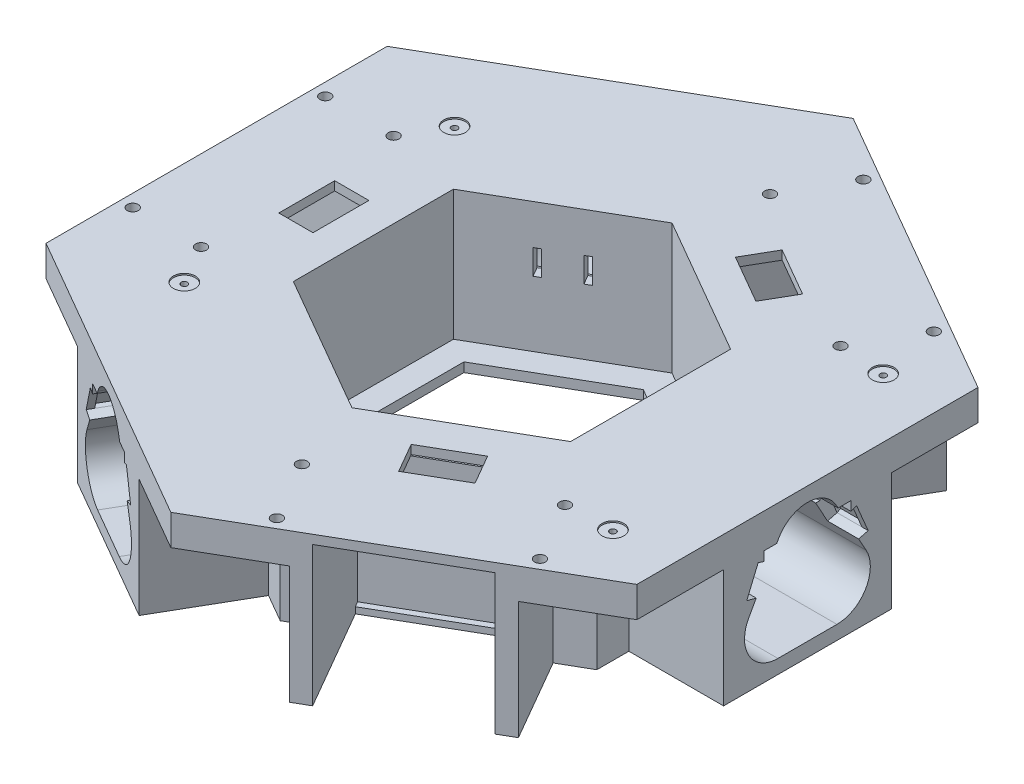
SolidWorks part; units mm, degrees
ref_plane "Plano frontal" through (0, 0, 0) normal (0, 0, 1) x (1, 0, 0)
ref_plane "Plano superior" through (0, 0, 0) normal (0, 1, 0) x (1, 0, 0)
ref_plane "Plano direito" through (0, 0, 0) normal (1, 0, 0) x (0, 0, -1)
sketch "Esboço1" plane through (0, 0, 0) normal (0, 1, 0) x (1, 0, 0)
  line L6 (-95.12, 54.9176) -> (-95.12, -54.9176)
  line L7 (95.12, 54.9176) -> (95.12, -54.9176)
  line L8 (-95.12, 54.9176) -> (0, 109.8351)
  line L9 (0, -109.8351) -> (95.12, -54.9176)
  line L10 (0, -109.8351) -> (-95.12, -54.9176)
  line L11 (95.12, 54.9176) -> (0, 109.8351)
extrude "Ressalto-extrusão1" add sketch "Esboço1" along normal blind 47.85 contours L6 L10 L9 L7 L11 L8
sketch "Esboço2" plane through (0, 47.85, 0) normal (0, 1, 0) x (1, 0, 0)
  line L6 (-36.62, 21.1426) -> (-36.62, -21.1426)
  line L7 (36.62, 21.1426) -> (36.62, -21.1426)
  line L8 (0, -42.2851) -> (36.62, -21.1426)
  line L9 (-36.62, 21.1426) -> (0, 42.2851)
  line L10 (36.62, 21.1426) -> (0, 42.2851)
  line L11 (0, -42.2851) -> (-36.62, -21.1426)
extrude "Corte-extrusão1" cut sketch "Esboço2" against normal through all
sketch "Esboço3" plane through (0, 47.85, 0) normal (0, 1, 0) x (1, 0, 0)
  line L1 (44.62, 25.7614) -> (44.62, -25.7614)
  line L3 (0, -51.5227) -> (-44.62, -25.7614)
  line L5 (44.62, -25.7614) -> (0, -51.5227)
  line L7 (-44.62, -25.7614) -> (-44.62, 25.7614)
  line L9 (-44.62, 25.7614) -> (0, 51.5227)
  line L11 (0, 51.5227) -> (44.62, 25.7614)
extrude "Corte-extrusão2" cut sketch "Esboço3" against normal blind 41.85 contours L11 L1 L5 L3 L7 L9
sketch "Esboço4" plane through (0, 0, 0) normal (0, -1, 0) x (-1, 0, 0)
  line L1 (-44.62, -25.7614) -> (-44.62, 25.7614)
  line L3 (0, 51.5227) -> (44.62, 25.7614)
  line L5 (44.62, 25.7614) -> (44.62, -25.7614)
  line L7 (44.62, -25.7614) -> (0, -51.5227)
  line L9 (-44.62, 25.7614) -> (0, 51.5227)
  line L11 (0, -51.5227) -> (-44.62, -25.7614)
extrude "Corte-extrusão3" cut sketch "Esboço4" against normal blind 3 contours L1 L9 L3 L5 L7 L11
sketch "Esboço5" plane through (-95.12, 0, 0) normal (-1, 0, 0) x (0, 0, 1)
  line L1 (0, 45) -> (-21.5, 45)
  line L2 (0, 45) -> (21.5, 45)
  line L3 (-21.5, 45) -> (-21.5, 0)
  line L4 (-54.9176, 0) -> (54.9176, 0) construction
  line L5 (21.5, 45) -> (21.5, 0)
  line L6 (-21.5, 0) -> (21.5, 0)
extrude "Corte-extrusão4" cut sketch "Esboço5" against normal blind 42.04
sketch "Esboço6" plane through (-53.08, 0, 0) normal (-1, 0, 0) x (0, 0, 1)
  line L0 (0, 0) -> (21.5, 0)
  line L1 (-21.5, 0) -> (21.5, 0) construction
  line L2 (21.5, 0) -> (21.5, 2)
  line L3 (21.5, 0) -> (21.5, 45) construction
  line L4 (0, 0) -> (-21.5, 0)
  line L5 (-21.5, 0) -> (-21.5, 2)
  line L6 (-21.5, 45) -> (-21.5, 0) construction
  line L7 (-21.5, 2) -> (21.5, 2)
extrude "Ressalto-extrusão2" add sketch "Esboço6" along normal blind 2
sketch "Esboço7" plane through (47.56, 0, -82.3763) normal (0.5, 0, -0.866) x (-0.866, 0, -0.5)
  line L1 (0, 45) -> (21.5, 45)
  line L2 (21.5, 45) -> (21.5, 0)
  line L3 (-54.9176, 0) -> (54.9176, 0) construction
  line L4 (0, 45) -> (-21.5, 45)
  line L5 (-21.5, 45) -> (-21.5, 0)
  line L6 (-21.5, 0) -> (21.5, 0)
extrude "Corte-extrusão5" cut sketch "Esboço7" against normal blind 42.04 contours L4 L5 L6 L2 L1
sketch "Esboço8" plane through (47.56, 0, 82.3763) normal (0.5, 0, 0.866) x (0.866, 0, -0.5)
  line L1 (0, 45) -> (21.5, 45)
  line L2 (21.5, 45) -> (21.5, 0)
  line L3 (-54.9176, 0) -> (54.9176, 0) construction
  line L4 (0, 45) -> (-21.5, 45)
  line L5 (-21.5, 45) -> (-21.5, 0)
  line L6 (-21.5, 0) -> (21.5, 0)
extrude "Corte-extrusão6" cut sketch "Esboço8" against normal blind 42.04
sketch "Esboço9" plane through (26.54, 0, 45.9686) normal (0.5, 0, 0.866) x (0.866, 0, -0.5)
  line L0 (0, 0) -> (21.5, 0)
  line L1 (-21.5, 0) -> (21.5, 0) construction
  line L2 (21.5, 0) -> (21.5, 2)
  line L3 (21.5, 0) -> (21.5, 45) construction
  line L4 (0, 0) -> (-21.5, 0)
  line L5 (-21.5, 0) -> (-21.5, 2)
  line L6 (-21.5, 45) -> (-21.5, 0) construction
  line L7 (-21.5, 2) -> (21.5, 2)
extrude "Ressalto-extrusão3" add sketch "Esboço9" along normal blind 2
sketch "Esboço10" plane through (26.54, 0, -45.9686) normal (0.5, 0, -0.866) x (-0.866, 0, -0.5)
  line L0 (0, 0) -> (21.5, 0)
  line L1 (-21.5, 0) -> (21.5, 0) construction
  line L2 (21.5, 0) -> (21.5, 2)
  line L3 (21.5, 45) -> (21.5, 0) construction
  line L4 (0, 0) -> (-21.5, 0)
  line L5 (-21.5, 0) -> (-21.5, 2)
  line L6 (-21.5, 45) -> (-21.5, 0) construction
  line L7 (-21.5, 2) -> (21.5, 2)
extrude "Ressalto-extrusão4" add sketch "Esboço10" along normal blind 2
sketch "Esboço11" plane through (0, 47.85, 0) normal (0, 1, 0) x (1, 0, 0)
  line L1 (-52.58, 0) -> (-52.58, 9)
  line L2 (-52.58, 9) -> (-63.58, 9)
  line L3 (-63.58, 9) -> (-63.58, -9)
  line L4 (-63.58, -9) -> (-52.58, -9)
  line L5 (-52.58, -9) -> (-52.58, 0)
  line L7 (26.29, 45.5356) -> (34.0842, 41.0356)
  line L8 (34.0842, 41.0356) -> (39.5842, 50.5619)
  line L9 (39.5842, 50.5619) -> (23.9958, 59.5619)
  line L10 (23.9958, 59.5619) -> (18.4958, 50.0356)
  line L11 (18.4958, 50.0356) -> (26.29, 45.5356)
  line L13 (26.29, -45.5356) -> (18.4958, -50.0356)
  line L14 (18.4958, -50.0356) -> (23.9958, -59.5619)
  line L15 (23.9958, -59.5619) -> (39.5842, -50.5619)
  line L16 (39.5842, -50.5619) -> (34.0842, -41.0356)
  line L17 (34.0842, -41.0356) -> (26.29, -45.5356)
extrude "Corte-extrusão7" cut sketch "Esboço11" against normal blind 2.85
sketch "Esboço12" plane through (95.12, 0, 0) normal (1, 0, 0) x (0, 0, -1)
  line L10 (-9.3154, 37.762) -> (-18.9028, 20.4605)
  line L11 (9.3154, 37.762) -> (18.9028, 20.4605)
  line L12 (-9.5, 4.5) -> (9.5, 4.5)
  arc A1 (-18.9028, 20.4605) -> (-9.5, 4.5) centre (-9.5, 15.25) ccw
  arc A3 (9.3154, 37.762) -> (-9.3154, 37.762) centre (0, 32.6) ccw
  arc A4 (9.5, 4.5) -> (18.9028, 20.4605) centre (9.5, 15.25) ccw
extrude "Corte-extrusão8" cut sketch "Esboço12" against normal blind 37.5 contours L10 A1 L12 A4 L11 A3
sketch "Esboço13" plane through (-47.56, 0, 82.3763) normal (-0.5, 0, 0.866) x (0.866, 0, 0.5)
  line L2 (-9.3154, 37.762) -> (-18.9028, 20.4605)
  line L4 (9.5, 4.5) -> (-9.5, 4.5)
  line L6 (9.3154, 37.762) -> (18.9028, 20.4605)
  arc A0 (9.3154, 37.762) -> (-9.3154, 37.762) centre (0, 32.6) ccw
  arc A1 (-18.9028, 20.4605) -> (-9.5, 4.5) centre (-9.5, 15.25) ccw
  arc A2 (9.5, 4.5) -> (18.9028, 20.4605) centre (9.5, 15.25) ccw
extrude "Corte-extrusão9" cut sketch "Esboço13" against normal blind 37.5
sketch "Esboço14" plane through (-47.56, 0, -82.3763) normal (-0.5, 0, -0.866) x (-0.866, 0, 0.5)
  line L0 (-9.3154, 37.762) -> (-18.9028, 20.4605)
  line L2 (9.3154, 37.762) -> (18.9028, 20.4605)
  line L4 (9.5, 4.5) -> (-9.5, 4.5)
  arc A0 (9.3154, 37.762) -> (-9.3154, 37.762) centre (0, 32.6) ccw
  arc A1 (-18.9028, 20.4605) -> (-9.5, 4.5) centre (-9.5, 15.25) ccw
  arc A2 (9.5, 4.5) -> (18.9028, 20.4605) centre (9.5, 15.25) ccw
extrude "Corte-extrusão10" cut sketch "Esboço14" against normal blind 37.5
sketch "Esboço15" plane through (95.12, 0, 0) normal (1, 0, 0) x (0, 0, -1)
  line L15 (-9.3154, 37.762) -> (-18.8809, 20.5)
  line L16 (9.3154, 37.762) -> (18.8809, 20.5)
  line L19 (-18.8809, 20.5) -> (18.8809, 20.5)
  arc A0 (9.3154, 37.762) -> (-9.3154, 37.762) centre (0, 32.6) ccw
extrude "Corte-extrusão11" cut sketch "Esboço15" against normal blind 47
sketch "Esboço16" plane through (-47.56, 0, -82.3763) normal (-0.5, 0, -0.866) x (-0.866, 0, 0.5)
  line L2 (9.3154, 37.762) -> (18.9028, 20.4605)
  line L3 (-9.3154, 37.762) -> (-18.9028, 20.4605)
  line L17 (18.8808, 20.5) -> (-18.8808, 20.5)
  arc A1 (-18.8808, 20.5) -> (-18.9028, 20.4605) centre (-9.5, 15.25) ccw
  arc A2 (18.9028, 20.4605) -> (18.8808, 20.5) centre (9.5, 15.25) ccw
  arc A5 (9.3154, 37.762) -> (-9.3154, 37.762) centre (0, 32.6) ccw
extrude "Corte-extrusão12" cut sketch "Esboço16" against normal blind 47 contours L3 A1 L17 A2 L2 A5
sketch "Esboço17" plane through (-47.56, 0, 82.3763) normal (-0.5, 0, 0.866) x (0.866, 0, 0.5)
  line L16 (-9.3154, 37.762) -> (-18.8809, 20.5)
  line L17 (9.3154, 37.762) -> (18.8809, 20.5)
  line L18 (18.8809, 20.5) -> (-18.8809, 20.5)
  arc A2 (9.3154, 37.762) -> (-9.3154, 37.762) centre (0, 32.6) ccw
extrude "Corte-extrusão13" cut sketch "Esboço17" against normal blind 47
sketch "Esboço22" plane through (95.12, 0, 0) normal (1, 0, 0) x (0, 0, -1)
  line L3 (14, 36.75) -> (-14, 36.75)
  line L4 (14, 31.75) -> (-14, 31.75)
  line L8 (14, 36.75) -> (14, 31.75)
  line L10 (-14, 36.75) -> (-14, 31.75)
extrude "Corte-extrusão17" cut sketch "Esboço22" against normal blind 47
sketch "Esboço23" plane through (-47.56, 0, -82.3763) normal (-0.5, 0, -0.866) x (-0.866, 0, 0.5)
  line L3 (14, 36.75) -> (-14, 36.75)
  line L4 (14, 31.75) -> (-14, 31.75)
  line L8 (14, 36.75) -> (14, 31.75)
  line L10 (-14, 36.75) -> (-14, 31.75)
extrude "Corte-extrusão18" cut sketch "Esboço23" against normal blind 47
sketch "Esboço24" plane through (-47.56, 0, 82.3763) normal (-0.5, 0, 0.866) x (0.866, 0, 0.5)
  line L3 (14, 36.75) -> (-14, 36.75)
  line L4 (14, 31.75) -> (-14, 31.75)
  line L8 (14, 36.75) -> (14, 31.75)
  line L10 (-14, 36.75) -> (-14, 31.75)
extrude "Corte-extrusão19" cut sketch "Esboço24" against normal blind 47
sketch "Esboço25" plane through (95.12, 0, 0) normal (1, 0, 0) x (0, 0, -1)
  line L3 (-18.8809, 20.5) -> (18.8809, 20.5) construction
  line L22 (-15.86, 34.37) -> (0, 29.25)
  line L23 (15.86, 34.37) -> (0, 29.25)
  line L24 (-19.55, 25.62) -> (0, 20.5)
  line L25 (0, 20.5) -> (19.55, 25.62)
  line L26 (19.55, 25.62) -> (15.86, 34.37)
  line L27 (-15.86, 34.37) -> (-19.55, 25.62)
extrude "Corte-extrusão20" cut sketch "Esboço25" against normal blind 10
sketch "Esboço26" plane through (-47.56, 0, -82.3763) normal (-0.5, 0, -0.866) x (-0.866, 0, 0.5)
  line L19 (18.8808, 20.5) -> (-18.8808, 20.5) construction
  line L20 (-15.86, 34.37) -> (0, 29.25)
  line L21 (0, 29.25) -> (15.86, 34.37)
  line L22 (-19.55, 25.62) -> (-15.86, 34.37)
  line L23 (-19.55, 25.62) -> (0, 20.5)
  line L24 (0, 20.5) -> (19.55, 25.62)
  line L25 (15.86, 34.37) -> (19.55, 25.62)
extrude "Corte-extrusão21" cut sketch "Esboço26" against normal blind 10 contours L23 L24 L25 L21 L20 L22
sketch "Esboço27" plane through (-47.56, 0, 82.3763) normal (-0.5, 0, 0.866) x (0.866, 0, 0.5)
  line L3 (-15.86, 34.37) -> (0, 29.25)
  line L4 (0, 29.25) -> (15.86, 34.37)
  line L5 (-19.55, 25.62) -> (-15.86, 34.37)
  line L6 (-19.55, 25.62) -> (0, 20.5)
  line L7 (0, 20.5) -> (19.55, 25.62)
  line L8 (15.86, 34.37) -> (19.55, 25.62)
extrude "Corte-extrusão22" cut sketch "Esboço27" against normal blind 10 contours L6 L5 L3 L4 L8 L7
sketch "Esboço28" plane through (22.3184, 10.868, -12.8856) normal (-0.798, -0.3886, 0.4607) x (0.4142, 0.2017, 0.8876)
  line L1 (-79.5509, 34.2548) -> (-89.3084, 36.4438) construction
  line L2 (-87.3569, 36.006) -> (-85.2781, 45.2719)
  line L3 (-77.4722, 43.5207) -> (-87.2296, 45.7097) construction
  line L4 (-85.2781, 45.2719) -> (-77.4722, 43.5207)
  line L5 (-77.4722, 43.5207) -> (-79.5509, 34.2548)
  line L7 (-87.3569, 36.006) -> (-79.5509, 34.2548)
extrude "Corte-extrusão23" cut sketch "Esboço28" against normal blind 1.5 draft 15 contours L5 L7 L2 L4 draft outward yes
sketch "Esboço29" plane through (-22.3184, 10.868, 12.8856) normal (0.798, -0.3886, -0.4607) x (-0.4142, 0.2017, -0.8876)
  line L1 (86.5602, -3.0112) -> (96.3177, -5.2002) construction
  line L2 (94.3662, -4.7624) -> (86.5602, -3.0112)
  line L3 (86.5602, -3.0112) -> (88.639, 6.2547)
  line L4 (88.639, 6.2547) -> (98.3964, 4.0657) construction
  line L5 (88.639, 6.2547) -> (86.5602, -3.0112) construction
  line L6 (88.639, 6.2547) -> (96.4449, 4.5035)
  line L7 (96.4449, 4.5035) -> (94.3662, -4.7624)
extrude "Corte-extrusão24" cut sketch "Esboço29" against normal blind 1.5 draft 15 contours L2 L3 L6 L7 draft outward yes
sketch "Esboço30" plane through (-22.3184, 10.868, -12.8856) normal (0.798, -0.3886, 0.4607) x (0.4142, -0.2017, -0.8876)
  line L1 (-86.5602, -3.0112) -> (-96.3177, -5.2002) construction
  line L2 (-94.3662, -4.7624) -> (-86.5602, -3.0112)
  line L3 (-86.5602, -3.0112) -> (-88.639, 6.2547)
  line L4 (-88.639, 6.2547) -> (-96.4449, 4.5035)
  line L5 (-88.639, 6.2547) -> (-98.3964, 4.0657) construction
  line L6 (-96.4449, 4.5035) -> (-94.3662, -4.7624)
extrude "Corte-extrusão25" cut sketch "Esboço30" against normal blind 1.5 draft 15 draft outward yes
sketch "Esboço31" plane through (22.3184, 10.868, 12.8856) normal (-0.798, -0.3886, -0.4607) x (-0.4142, -0.2017, 0.8876)
  line L1 (77.4722, 43.5207) -> (87.2296, 45.7097) construction
  line L2 (85.2781, 45.2719) -> (77.4722, 43.5207)
  line L3 (77.4722, 43.5207) -> (79.5509, 34.2548)
  line L4 (79.5509, 34.2548) -> (87.3569, 36.006)
  line L5 (79.5509, 34.2548) -> (89.3084, 36.4438) construction
  line L6 (87.3569, 36.006) -> (85.2781, 45.2719)
extrude "Corte-extrusão26" cut sketch "Esboço31" against normal blind 1.5 draft 15 draft outward yes
sketch "Esboço32" plane through (0, 10.868, -25.7711) normal (0, -0.3886, 0.9214) x (1, 0, 0)
  line L1 (85.12, 16.0101) -> (95.12, 16.0101) construction
  line L2 (93.12, 16.0101) -> (85.12, 16.0101)
  line L3 (85.12, 16.0101) -> (85.12, 25.5063)
  line L4 (85.12, 25.5063) -> (93.12, 25.5063)
  line L5 (85.12, 25.5063) -> (95.12, 25.5063) construction
  line L6 (93.12, 25.5063) -> (93.12, 16.0101)
extrude "Corte-extrusão27" cut sketch "Esboço32" against normal blind 1.5 draft 15 draft outward yes
sketch "Esboço33" plane through (0, 10.868, 25.7711) normal (0, -0.3886, -0.9214) x (-1, 0, 0)
  line L0 (-85.12, 16.0101) -> (-93.12, 16.0101)
  line L1 (-85.12, 16.0101) -> (-95.12, 16.0101) construction
  line L2 (-93.12, 16.0101) -> (-93.12, 25.5063)
  line L3 (-85.12, 25.5063) -> (-95.12, 25.5063) construction
  line L4 (-93.12, 25.5063) -> (-85.12, 25.5063)
  line L5 (-85.12, 25.5063) -> (-85.12, 16.0101)
extrude "Corte-extrusão28" cut sketch "Esboço33" against normal blind 1.5 draft 15 draft outward yes
sketch "Esboço34" plane through (95.12, 0, 0) normal (1, 0, 0) x (0, 0, -1)
  line L3 (-5, 27) -> (-5, 35)
  line L4 (-5, 35) -> (-7, 35)
  line L5 (-7, 35) -> (-7, 27)
  line L6 (-7, 27) -> (-5, 27)
  line L8 (5, 27) -> (5, 35)
  line L9 (5, 35) -> (7, 35)
  line L10 (7, 35) -> (7, 27)
  line L11 (5, 27) -> (7, 27)
extrude "Corte-extrusão29" cut sketch "Esboço34" against normal blind 78.5
sketch "Esboço35" plane through (-47.56, 0, -82.3763) normal (-0.5, 0, -0.866) x (-0.866, 0, 0.5)
  line L4 (-5, 27) -> (-5, 35)
  line L5 (-5, 35) -> (-7, 35)
  line L6 (-7, 35) -> (-7, 27)
  line L7 (-7, 27) -> (-5, 27)
  line L9 (5, 27) -> (5, 35)
  line L10 (5, 35) -> (7, 35)
  line L11 (7, 35) -> (7, 27)
  line L12 (5, 27) -> (7, 27)
extrude "Corte-extrusão30" cut sketch "Esboço35" against normal blind 78.5
sketch "Esboço36" plane through (-47.56, 0, 82.3763) normal (-0.5, 0, 0.866) x (0.866, 0, 0.5)
  line L4 (-5, 27) -> (-5, 35)
  line L5 (-5, 35) -> (-7, 35)
  line L6 (-7, 35) -> (-7, 27)
  line L7 (-7, 27) -> (-5, 27)
  line L9 (5, 27) -> (5, 35)
  line L10 (5, 35) -> (7, 35)
  line L11 (7, 35) -> (7, 27)
  line L12 (5, 27) -> (7, 27)
extrude "Corte-extrusão31" cut sketch "Esboço36" against normal blind 78.5
sketch "Esboço38" plane through (0, 0, 0) normal (0, -1, 0) x (-1, 0, 0)
  line L30 (-8.9273, 69.4626) -> (0, 74.6167)
  line L32 (8.9273, 69.4626) -> (0, 74.6167)
  line L46 (64.62, 27) -> (64.62, 37.3084)
  line L47 (126.8267, 27) -> (126.8267, -27)
  line L58 (55.6927, 42.4626) -> (64.62, 37.3084)
  line L61 (64.62, -27) -> (64.62, -37.3084)
  line L64 (8.9273, -69.4626) -> (0, -74.6167)
  line L67 (-55.6927, -42.4626) -> (-64.62, -37.3084)
  line L70 (-64.62, 27) -> (-64.62, 37.3084)
  line L72 (55.6927, -42.4626) -> (64.62, -37.3084)
  line L73 (86.796, -96.3351) -> (40.0306, -123.3351)
  line L74 (-8.9273, -69.4626) -> (0, -74.6167)
  line L75 (-40.0306, -123.3351) -> (-86.796, -96.3351)
  line L76 (-64.62, -27) -> (-64.62, -37.3084)
  line L77 (-40.0306, -123.3351) -> (-8.9273, -69.4626)
  line L78 (-86.796, -96.3351) -> (-55.6927, -42.4626)
  line L79 (-40.0306, 123.3351) -> (-86.796, 96.3351)
  line L80 (-55.6927, 42.4626) -> (-64.62, 37.3084)
  line L81 (-126.8267, 27) -> (-126.8267, -27)
  line L82 (86.796, 96.3351) -> (144.1652, 53.1986)
  line L83 (-86.796, 96.3351) -> (-55.6927, 42.4626)
  line L84 (-40.0306, 123.3351) -> (-8.9273, 69.4626)
  line L85 (144.1652, 53.1986) -> (157.5659, 0)
  line L87 (157.5659, 0) -> (144.1652, -63.213)
  line L88 (-126.8267, -27) -> (-64.62, -27)
  line L89 (-126.8267, 27) -> (-64.62, 27)
  line L90 (144.1652, -63.213) -> (119.6711, -105.6381)
  line L91 (119.6711, -105.6381) -> (86.796, -138.7939)
  line L92 (86.796, -138.7939) -> (8.9273, -147.887)
  line L93 (126.8267, 27) -> (64.62, 27)
  line L94 (126.8267, -27) -> (64.62, -27)
  line L95 (8.9273, -147.887) -> (-79.3373, -147.887)
  line L96 (-79.3373, -147.887) -> (-101.3016, -126.1087)
  line L97 (-101.3016, -126.1087) -> (-135.3677, -74.6167)
  line L98 (40.0306, 123.3351) -> (8.9273, 69.4626)
  line L99 (86.796, 96.3351) -> (55.6927, 42.4626)
  line L100 (-135.3677, -74.6167) -> (-152.3432, -27)
  line L101 (-152.3432, -27) -> (-152.3432, 37.3084)
  line L102 (-152.3432, 37.3084) -> (-101.3016, 133.3327)
  line L103 (86.796, -96.3351) -> (55.6927, -42.4626)
  line L104 (40.0306, -123.3351) -> (8.9273, -69.4626)
  line L105 (-101.3016, 133.3327) -> (-48.9949, 151.9802)
  line L106 (-48.9949, 151.9802) -> (18.3094, 159.8396)
  line L107 (18.3094, 159.8396) -> (40.0306, 123.3351)
extrude "Corte-extrusão37" cut sketch "Esboço38" against normal blind 38
sketch "Esboço42" plane through (0, 47.85, 0) normal (0, 1, 0) x (1, 0, 0)
  circle A0 centre (18.7132, 94.4122) radius 1.75
  circle A1 centre (61.4068, -44.3597) radius 1.75
  circle A2 centre (-91.12, 31) radius 1.75
  circle A3 centre (18.7132, -94.4122) radius 1.75
  circle A5 centre (-91.12, -31) radius 1.75
  circle A6 centre (7.7132, -75.3597) radius 1.75
  circle A7 centre (72.4068, -63.4122) radius 1.75
  circle A9 centre (-69.12, 31) radius 1.75
  circle A10 centre (61.4068, 44.3597) radius 1.75
  circle A12 centre (7.7132, 75.3597) radius 1.75
  circle A13 centre (-69.12, -31) radius 1.75
  circle A14 centre (72.4068, 63.4122) radius 1.75
extrude "Corte-extrusão38" cut sketch "Esboço42" against normal through all
sketch "Esboço43" plane through (0, 47.85, 0) normal (0, 1, 0) x (1, 0, 0)
  circle A0 centre (-62, 43.5) radius 3.5
  circle A1 centre (76, 43.5) radius 3.5
  circle A2 centre (-62, -43.5) radius 3.5
  circle A3 centre (76, -43.5) radius 3.5
extrude "Corte-extrusão39" cut sketch "Esboço43" against normal blind 0.5
sketch "Esboço44" plane through (0, 47.85, 0) normal (0, 1, 0) x (1, 0, 0)
  circle A0 centre (-62, 43.5) radius 1
  circle A1 centre (76, 43.5) radius 1
  circle A2 centre (76, -43.5) radius 1
  circle A3 centre (-62, -43.5) radius 1
extrude "Corte-extrusão40" cut sketch "Esboço44" against normal blind 8
sketch "Esboço45" plane through (26.29, 0, 45.5356) normal (0.5, 0, 0.866) x (0.866, 0, -0.5)
  line L1 (9, 47.85) -> (-9, 47.85)
  line L2 (9, 47.85) -> (9, 45)
  line L3 (9, 45) -> (-9, 45)
  line L4 (-9, 47.85) -> (-9, 45)
extrude "Ressalto-extrusão5" add sketch "Esboço45" along normal blind 2.5
sketch "Esboço46" plane through (31.79, 0, 55.0619) normal (-0.5, 0, -0.866) x (-0.866, 0, 0.5)
  line L1 (9, 47.85) -> (-9, 47.85)
  line L2 (9, 47.85) -> (9, 45)
  line L3 (9, 45) -> (-9, 45)
  line L4 (-9, 47.85) -> (-9, 45)
extrude "Corte-extrusão41" cut sketch "Esboço46" against normal blind 2.5
sketch "Esboço47" plane through (26.54, 0, 45.9686) normal (0.5, 0, 0.866) x (0.866, 0, -0.5)
  line L1 (-21.5, 45) -> (21.5, 45)
  line L2 (-21.5, 45) -> (-21.5, 2)
  line L3 (-21.5, 2) -> (21.5, 2)
  line L4 (21.5, 45) -> (21.5, 2)
extrude "Ressalto-extrusão6" add sketch "Esboço47" along normal blind 2.5
sketch "Esboço48" plane through (27.54, 0, 47.7007) normal (0.5, 0, 0.866) x (0.866, 0, -0.5)
  line L1 (21.5, 2) -> (-21.5, 2)
  line L2 (21.5, 2) -> (21.5, 0)
  line L3 (21.5, 0) -> (-21.5, 0)
  line L4 (-21.5, 2) -> (-21.5, 0)
extrude "Ressalto-extrusão7" add sketch "Esboço48" along normal blind 2.5
sketch "Esboço49" plane through (27.54, 0, -47.7007) normal (0.5, 0, -0.866) x (-0.866, 0, -0.5)
  line L1 (21.5, 2) -> (-21.5, 2)
  line L2 (21.5, 2) -> (21.5, 0)
  line L3 (21.5, 0) -> (-21.5, 0)
  line L4 (-21.5, 2) -> (-21.5, 0)
extrude "Ressalto-extrusão8" add sketch "Esboço49" along normal blind 2.5
sketch "Esboço50" plane through (26.54, 0, -45.9686) normal (0.5, 0, -0.866) x (-0.866, 0, -0.5)
  line L1 (21.5, 45) -> (-21.5, 45)
  line L2 (21.5, 45) -> (21.5, 2)
  line L3 (21.5, 2) -> (-21.5, 2)
  line L4 (-21.5, 45) -> (-21.5, 2)
extrude "Ressalto-extrusão9" add sketch "Esboço50" along normal blind 2.5
sketch "Esboço51" plane through (26.29, 0, -45.5356) normal (0.5, 0, -0.866) x (-0.866, 0, -0.5)
  line L1 (9, 47.85) -> (-9, 47.85)
  line L2 (9, 47.85) -> (9, 45)
  line L3 (9, 45) -> (-9, 45)
  line L4 (-9, 47.85) -> (-9, 45)
extrude "Ressalto-extrusão10" add sketch "Esboço51" along normal blind 2.5
sketch "Esboço52" plane through (31.79, 0, -55.0619) normal (-0.5, 0, 0.866) x (0.866, 0, 0.5)
  line L1 (-9, 47.85) -> (9, 47.85)
  line L2 (-9, 47.85) -> (-9, 45)
  line L3 (-9, 45) -> (9, 45)
  line L4 (9, 47.85) -> (9, 45)
extrude "Corte-extrusão42" cut sketch "Esboço52" against normal blind 2.5
sketch "Esboço53" plane through (-55.08, 0, 0) normal (-1, 0, 0) x (0, 0, 1)
  line L1 (21.5, 2) -> (-21.5, 2)
  line L2 (21.5, 2) -> (21.5, 0)
  line L3 (21.5, 0) -> (-21.5, 0)
  line L4 (-21.5, 2) -> (-21.5, 0)
extrude "Ressalto-extrusão11" add sketch "Esboço53" along normal blind 2.5
sketch "Esboço54" plane through (-53.08, 0, 0) normal (-1, 0, 0) x (0, 0, 1)
  line L1 (-21.5, 45) -> (21.5, 45)
  line L2 (-21.5, 45) -> (-21.5, 2)
  line L3 (-21.5, 2) -> (21.5, 2)
  line L4 (21.5, 45) -> (21.5, 2)
extrude "Ressalto-extrusão12" add sketch "Esboço54" along normal blind 2.5
sketch "Esboço55" plane through (-52.58, 0, 0) normal (-1, 0, 0) x (0, 0, 1)
  line L1 (-9, 47.85) -> (9, 47.85)
  line L2 (-9, 47.85) -> (-9, 45)
  line L3 (-9, 45) -> (9, 45)
  line L4 (9, 47.85) -> (9, 45)
extrude "Ressalto-extrusão14" add sketch "Esboço55" along normal blind 2.5
sketch "Esboço56" plane through (-63.58, 0, 0) normal (1, 0, 0) x (0, 0, -1)
  line L1 (-9, 47.85) -> (9, 47.85)
  line L2 (-9, 47.85) -> (-9, 45)
  line L3 (-9, 45) -> (9, 45)
  line L4 (9, 47.85) -> (9, 45)
extrude "Corte-extrusão43" cut sketch "Esboço56" against normal blind 2.5
